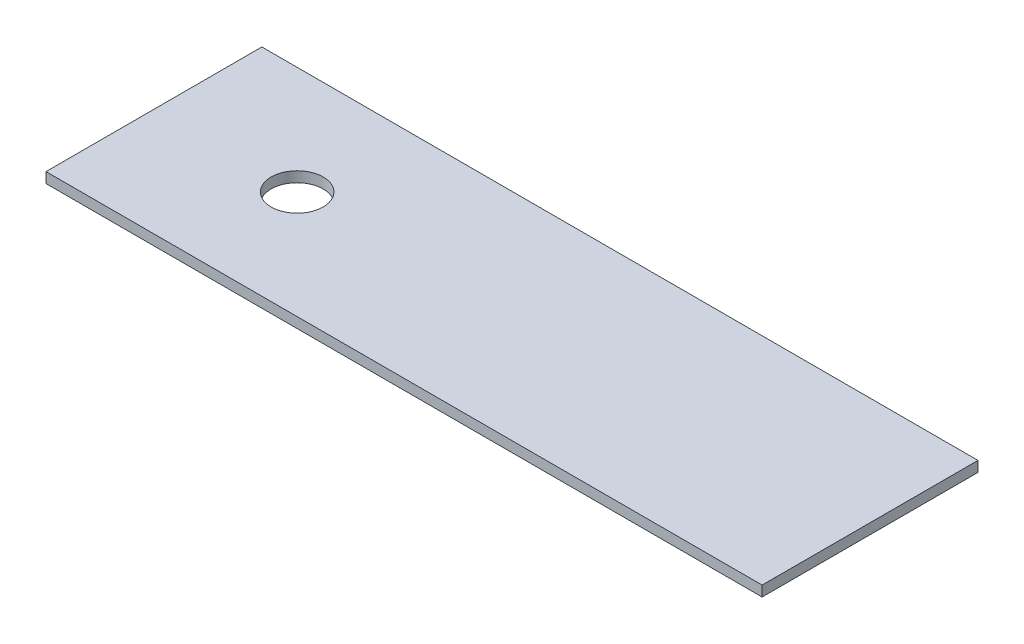
SolidWorks part; units mm, degrees
ref_plane "Front Plane" through (0, 0, 0) normal (0, 0, 1) x (1, 0, 0)
ref_plane "Top Plane" through (0, 0, 0) normal (0, 1, 0) x (1, 0, 0)
ref_plane "Right Plane" through (0, 0, 0) normal (1, 0, 0) x (0, 0, -1)
sketch "Sketch1" plane through (0, 0, 0) normal (0, 1, 0) x (1, 0, 0)
  line L0 (0, 0) -> (-41.3, 0) construction
  line L1 (206.5, -62.25) -> (-206.5, -62.25)
  line L2 (206.5, -62.25) -> (206.5, 62.25)
  line L3 (206.5, 62.25) -> (-206.5, 62.25)
  line L4 (-206.5, -62.25) -> (-206.5, 62.25)
  line L5 (206.5, -62.25) -> (-206.5, 62.25) construction
  line L6 (206.5, 62.25) -> (-206.5, -62.25) construction
  line L7 (-41.3, 0) -> (-82.6, 0) construction
  line L8 (-82.6, 0) -> (-123.9, 0) construction
  line L9 (-123.9, 0) -> (-165.2, 0) construction
  line L10 (-165.2, 0) -> (-206.5, 0) construction
  circle A0 centre (-123.9, 0) radius 15
  point P0 (0, 0)
  dimension "D2" = 30
  dimension "D1" = 124.5
  dimension "D3" = 413
extrude "Boss-Extrude1" add sketch "Sketch1" along normal blind 6
